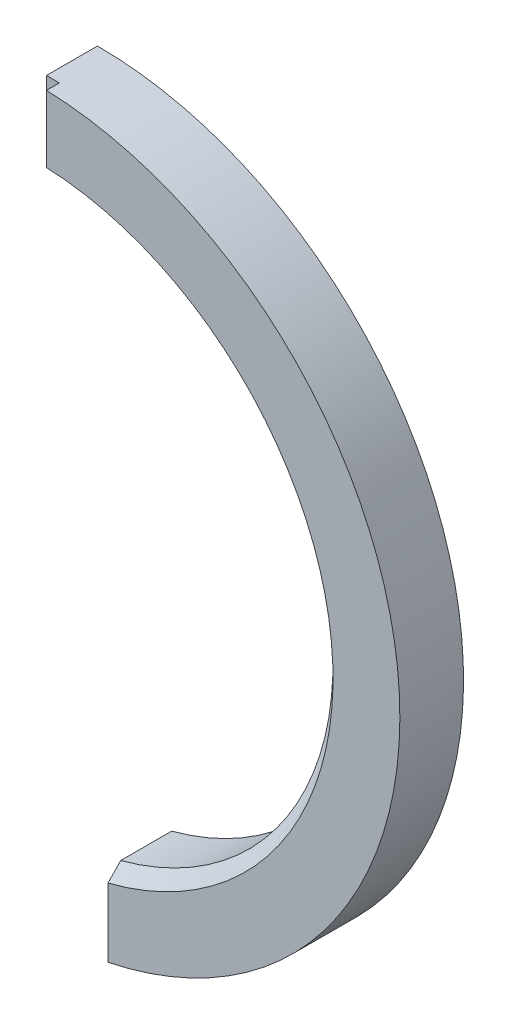
SolidWorks part; units mm, degrees
material "ABS"
ref_plane "Front Plane" through (0, 0, 0) normal (1, 0, 0) x (0, 1, 0)
ref_plane "Top Plane" through (0, 0, 0) normal (0, 0, 1) x (0, 1, 0)
ref_plane "Right Plane" through (0, 0, 0) normal (0, 1, 0) x (-1, 0, 0)
sketch "Sketch1" plane through (0, 0, 0) normal (0, 0, 1) x (0, 1, 0)
  circle A0 centre (0, 0) radius 57.5
  circle A1 centre (0, 0) radius 45
  dimension "D1" = 90
extrude "Boss-Extrude1" add sketch "Sketch1" along normal blind 10
sketch "Sketch2" plane through (0, 0, 0) normal (0, 0, -1) x (1, 0, 0)
  line L0 (0, 0) -> (0, 57.8453) construction
  line L1 (11.6505, 56.6599) -> (11.6505, 43.4657)
  line L3 (-11.6505, 43.4657) -> (-11.6505, 56.6599)
  circle A0 centre (0, 0) radius 57.8453 construction
  circle A5 centre (0, 0) radius 45 construction
  arc A10 (11.6505, 56.6599) -> (-11.6505, 56.6599) centre (0, 0) ccw
  spline S0 degree 2 poles (11.6505, 43.4657) (-0.6792, 46.4064) (-11.6505, 43.4657) knots 0 0 0 0.575547 0.575547 0.575547
  point P5 (0, 57.8453)
extrude "Cut-Extrude2" cut sketch "Sketch2" against normal blind 10
fillet "Chamfer1" radius 2 1 edges at (0, 45, 10) type face fillet profile chamfer first side face at (0, 0.6817, 10) second side face at (0, 0.7672, 5)
sketch "Sketch3" plane through (0, 0, 0) normal (0, 0, 1) x (0, 1, 0)
  line L1 (-57.4149, 0) -> (66.6982, 0)
  line L2 (-57.4149, 0) -> (-57.4149, -66.8765)
  line L3 (-57.4149, -66.8765) -> (66.6982, -66.8765)
  line L4 (66.6982, 0) -> (66.6982, -66.8765)
extrude "Cut-Extrude3" cut sketch "Sketch3" along normal blind 10
sketch "Sketch5" plane through (0, 0, 0) normal (0, 0, -1) x (1, 0, 0)
  line L0 (0, -51.25) -> (-2, -51.25) construction
  line L1 (0, -57.5) -> (0, -45) construction
  circle A0 centre (-6, -51.25) radius 4
  point P6 (0, 0)
  dimension "D2" = 8
  dimension "D1" = 2
extrude "Cut-Extrude4" cut sketch "Sketch5" against normal blind 3 from offset 2 offset against normal yes
sketch "Sketch6" plane through (0, 0, 0) normal (1, 0, 0) x (0, 1, 0)
  line L2 (57.5, 10) -> (57.5, 8)
  line L3 (57.5, 0) -> (57.5, 10) construction
  line L4 (57.5, 8) -> (45, 8)
  line L5 (57.5, 10) -> (45, 10)
  line L6 (47, 10) -> (-45.5331, 10) construction
  line L7 (45, 10) -> (45, 8)
sketch "Sketch7" plane through (0, 0, 0) normal (1, 0, 0) x (0, 1, 0)
  line L0 (45, 8) -> (57.5, 8)
  line L1 (57.5, 0) -> (57.5, 10) construction
  line L2 (57.5, 8) -> (57.5, 10)
  line L3 (57.5, 10) -> (45, 10)
  line L4 (47, 10) -> (-45.5331, 10) construction
  line L5 (45, 10) -> (45, 8)
extrude "Cut-Extrude8" cut sketch "Sketch7" against normal blind 2
mirror "Mirror2" about plane through (0, 0, 0) normal (1, 0, 0) of "Chamfer1", "Boss-Extrude1", "Cut-Extrude2", "Cut-Extrude3", "Cut-Extrude8", "Cut-Extrude4"
